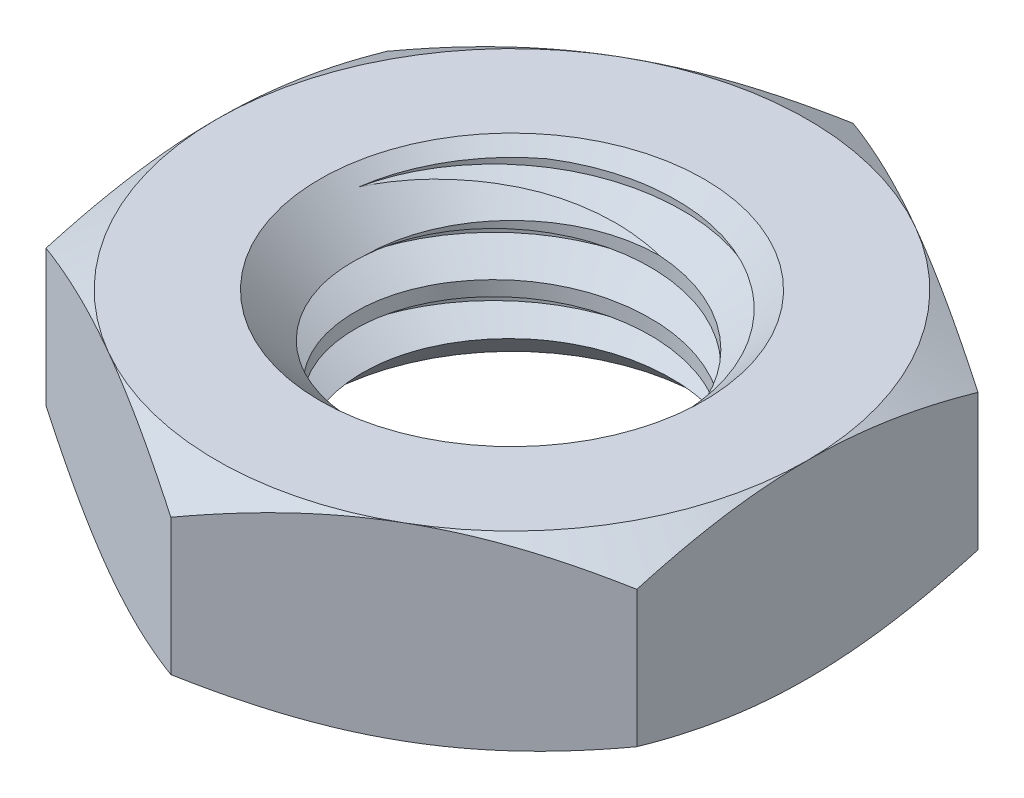
SolidWorks part; units mm, degrees
ref_plane "Front Plane" through (0, 0, 0) normal (0, 0, 1) x (1, 0, 0)
ref_plane "Top Plane" through (0, 0, 0) normal (0, 1, 0) x (1, 0, 0)
ref_plane "Right Plane" through (0, 0, 0) normal (1, 0, 0) x (0, 0, -1)
sketch "Sketch2" plane through (0, 0, 0) normal (0, 1, 0) x (1, 0, 0)
  line L0 (5, 2.8868) -> (5, -2.8868)
  line L1 (-5, 2.8868) -> (-5, -2.8868)
  line L2 (5, 2.8868) -> (0, 5.7735)
  line L3 (0, 5.7735) -> (-5, 2.8868)
  line L4 (-5, -2.8868) -> (0, -5.7735)
  line L5 (0, -5.7735) -> (5, -2.8868)
  line L6 (0, 5.7735) -> (0, -5.7735) construction
  circle A0 centre (0, 0) radius 2.5
  point P8 (0, 0)
  dimension "D3" = 5
  dimension "D1" = 10
  dimension "D2" = 120
extrude "Boss-Extrude1" add sketch "Sketch2" along normal blind 3.2
sketch "Sketch3" plane through (0, 0, 0) normal (0, 0, 1) x (1, 0, 0)
  line L0 (2.5, 2.5726) -> (6.5092, 1.1134)
  line L1 (2.5, 0) -> (6.3128, 0)
  line L2 (6.3128, 0.574) -> (6.3128, 0) construction
  line L3 (0, 0) -> (5, 0) construction
  line L4 (2.5, 0) -> (2.5, 2.5726)
  line L5 (2.5, 0) -> (0, 0) construction
  line L6 (0, 0) -> (0, 3.2) construction
  arc A0 (6.3128, 0) -> (6.5092, 1.1134) centre (6.3128, 0.574) ccw
  dimension "D1" = 3.8128
  dimension "D2" = 2.5726
  dimension "D3" = 0.574
  dimension "D4" = 2.5
revolve "Revolve1" [suppressed] add sketch "Sketch3" angle 360 about L6
sketch "Sketch4" plane through (0, 0, 0) normal (0, 0, 1) x (1, 0, 0)
  line L0 (-6, 2.6226) -> (0, 6.0868)
  line L1 (0, 6.0868) -> (0, 0) construction
  line L2 (-6, 2.6226) -> (-6, 7.2)
  line L3 (-6, 7.2) -> (0, 7.2)
  line L4 (0, 7.2) -> (0, 6.0868)
  line L5 (-5, 3.2) -> (0, 3.2) construction
  line L6 (-5, 1.6) -> (5, 1.6) construction
  line L7 (-5, 3.2) -> (-5, 0) construction
  line L8 (5, 3.2) -> (5, 0) construction
  line L9 (-6, 0.5774) -> (-6, -4)
  line L10 (-6, -4) -> (0, -4)
  line L11 (0, -4) -> (0, -2.8868)
  line L12 (-6, 0.5774) -> (0, -2.8868)
  dimension "D1" = 30
  dimension "D2" = 6
  dimension "D3" = 4
revolve "Cut-Revolve2" cut sketch "Sketch4" angle 360 about L1
chamfer "Chamfer1" distance 0.75 angle 45 2 edges at (0, 0, 2.5) (0, 3.2, 2.5)
thread "Thread1" pitch 1 method cut profile "Thread Profile1" start angle 0, offset 2, length 0, pitch 1, diameter 5
ref_plane "Plane1" through (-2.5, 4.45, 0) normal (0, 0, 1) x (-1, 0, 0)
sketch "Thread Profile1" plane through (-2.5, 4.45, 0) normal (0, 0, 1) x (-1, 0, 0)
  line L0 (0, 0) -> (0, 1) construction
  line L1 (0, 0) -> (0.5413, 0.3125)
  line L2 (0.5413, 0.3125) -> (0.5413, 0.4375)
  line L3 (0.5413, 0.4375) -> (0, 0.75)
  line L4 (0.5413, 0.375) -> (0, 0.375) construction
  line L11 (0, 0) -> (0, 0.75)
  point P2 (0, 0)
  dimension "Pitch" = 1
  dimension "Profile_Angle" = 60
  dimension "Profile_Land" = 0.125
  dimension "Profile_Height" = 0.5413
